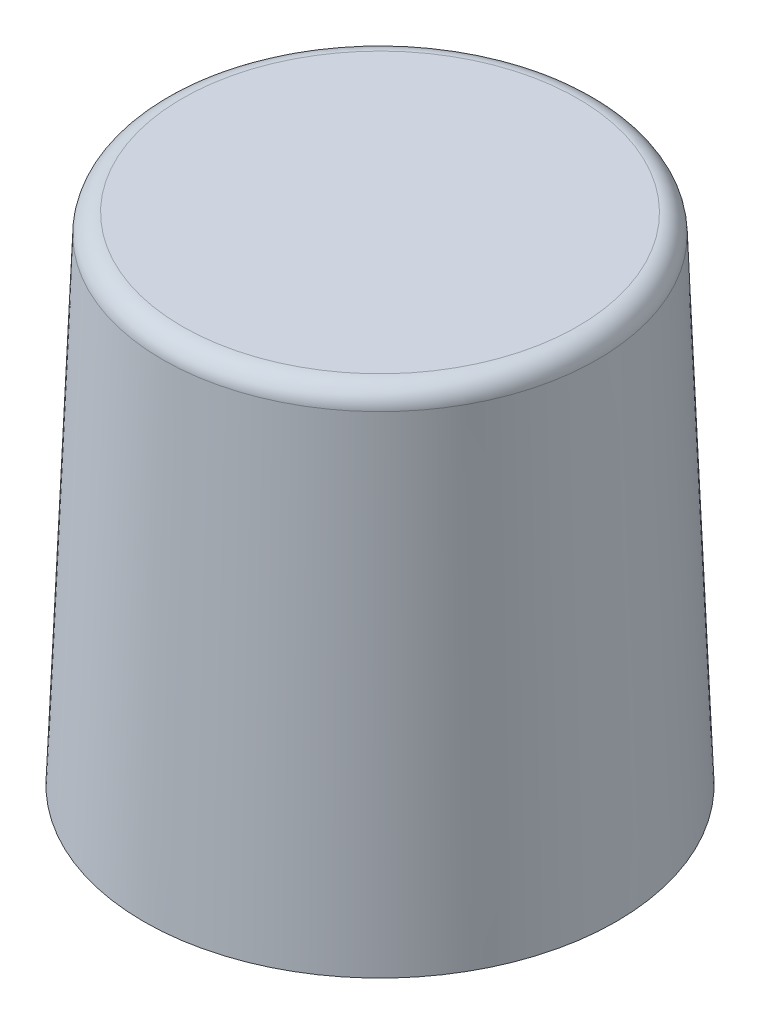
SolidWorks part; units mm, degrees
material "Silicon Rubber"
ref_plane "Front" through (0, 0, 0) normal (0, 0, 1) x (1, 0, 0)
ref_plane "Top" through (0, 0, 0) normal (0, 1, 0) x (1, 0, 0)
ref_plane "Right" through (0, 0, 0) normal (1, 0, 0) x (0, 0, -1)
sketch "Sketch1" plane through (0, 0, 0) normal (0, 0, 1) x (1, 0, 0)
  line L0 (0, 0) -> (2.75, 0)
  line L1 (2.75, 0) -> (3, -6.3)
  line L2 (3, -6.3) -> (1.5, -6.3)
  line L3 (1.5, -6.3) -> (1.5, -0.3)
  line L4 (1.5, -0.3) -> (0, -0.3)
  line L5 (0, -0.3) -> (0, 0)
  line L6 (0, 0) -> (0, 10.7204) construction
  dimension "D1" = 5.5
  dimension "D2" = 6
  dimension "D3" = 6.3
  dimension "D4" = 6
  dimension "D5" = 3
revolve "Revolve1" add sketch "Sketch1" angle 360 about L6
fillet "Fillet1" radius 0.25 1 edges at (0, 0, -2.75)
